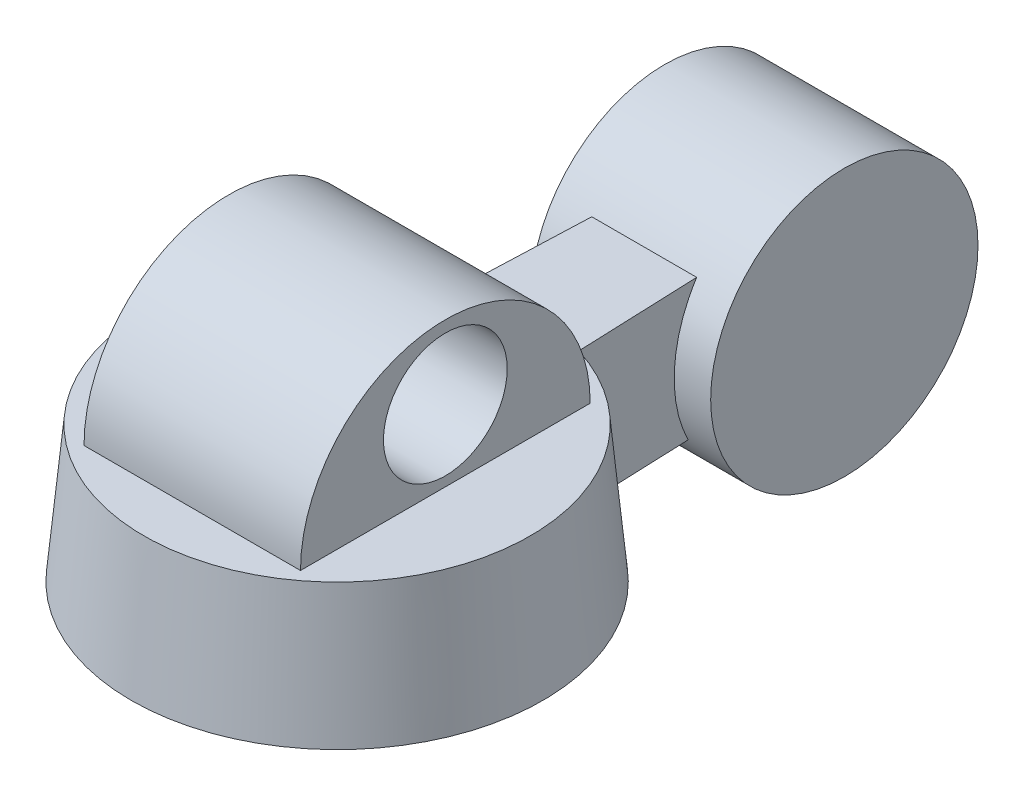
SolidWorks part; units mm, degrees
ref_plane "Front Plane" through (0, 0, 0) normal (0, 0, 1) x (1, 0, 0)
ref_plane "Top Plane" through (0, 0, 0) normal (0, 1, 0) x (1, 0, 0)
ref_plane "Right Plane" through (0, 0, 0) normal (1, 0, 0) x (0, 0, -1)
sketch "Sketch1" plane through (0, 0, 0) normal (0, 0, 1) x (1, 0, 0)
  line L0 (-40.3145, 0) -> (-46.3804, 0)
  line L1 (-46.3804, 0) -> (-43.5102, 30.6558)
  line L2 (-43.5102, 30.6558) -> (0, 30.6558)
  line L3 (0, 0) -> (0, -34.4351) construction
  line L4 (0, 11.7018) -> (0, 30.6558)
  line L5 (0, 11.7018) -> (-40.3145, 11.7018)
  line L6 (-40.3145, 11.7018) -> (-40.3145, 0)
revolve "Revolve1" add sketch "Sketch1" angle 360 about L3
sketch "Sketch2" plane through (0, 0, 0) normal (1, 0, 0) x (0, 0, -1)
  line L0 (0, 30.6558) -> (-32.6253, 30.6558)
  line L1 (43.5102, 30.6558) -> (-43.5102, 30.6558) construction
  line L2 (0, 30.6558) -> (32.6253, 30.6558)
  arc A0 (-32.6253, 30.6558) -> (32.6253, 30.6558) centre (0, 30.6558) cw
  circle A1 centre (0, 46.7345) radius 13.9352
  dimension "D1" = 32.6253
  dimension "D3" = 27.8704
  dimension "D2" = 16.0787
extrude "Boss-Extrude1" add sketch "Sketch2" along normal blind 24.3806 and the other way blind 24.3806
sketch "Sketch4" plane through (0, 0, 0) normal (0, 1, 0) x (1, 0, 0)
  line L0 (-12.7279, 45.6093) -> (12.7279, 45.6093) construction
  line L1 (12.7279, 45.6093) -> (10.7808, 95.9546)
  line L2 (10.7808, 95.9546) -> (-10.7808, 95.9546)
  line L3 (-10.7808, 95.9546) -> (-12.7279, 45.6093)
  line L4 (0, 0) -> (0, 60.8523) construction
  line L5 (-12.7279, 45.6093) -> (-12.9276, 40.4457)
  line L6 (-12.9276, 40.4457) -> (12.9276, 40.4457)
  line L7 (12.9276, 40.4457) -> (12.7279, 45.6093)
  point P5 (0, 95.9546)
  point P9 (0, 45.6093)
  dimension "D1" = 21.5616
  dimension "D2" = 25.4559
  dimension "D3" = 50.3453
  dimension "D4" = 45.6093
extrude "Boss-Extrude2" add sketch "Sketch4" along normal blind 30.6558
sketch "Sketch5" plane through (0, 0, 0) normal (1, 0, 0) x (0, 0, -1)
  circle A0 centre (94.0135, 13.638) radius 30.1061
  dimension "D1" = 60.2122
extrude "Boss-Extrude3" add sketch "Sketch5" along normal blind 20.2366 and the other way blind 20.2366
